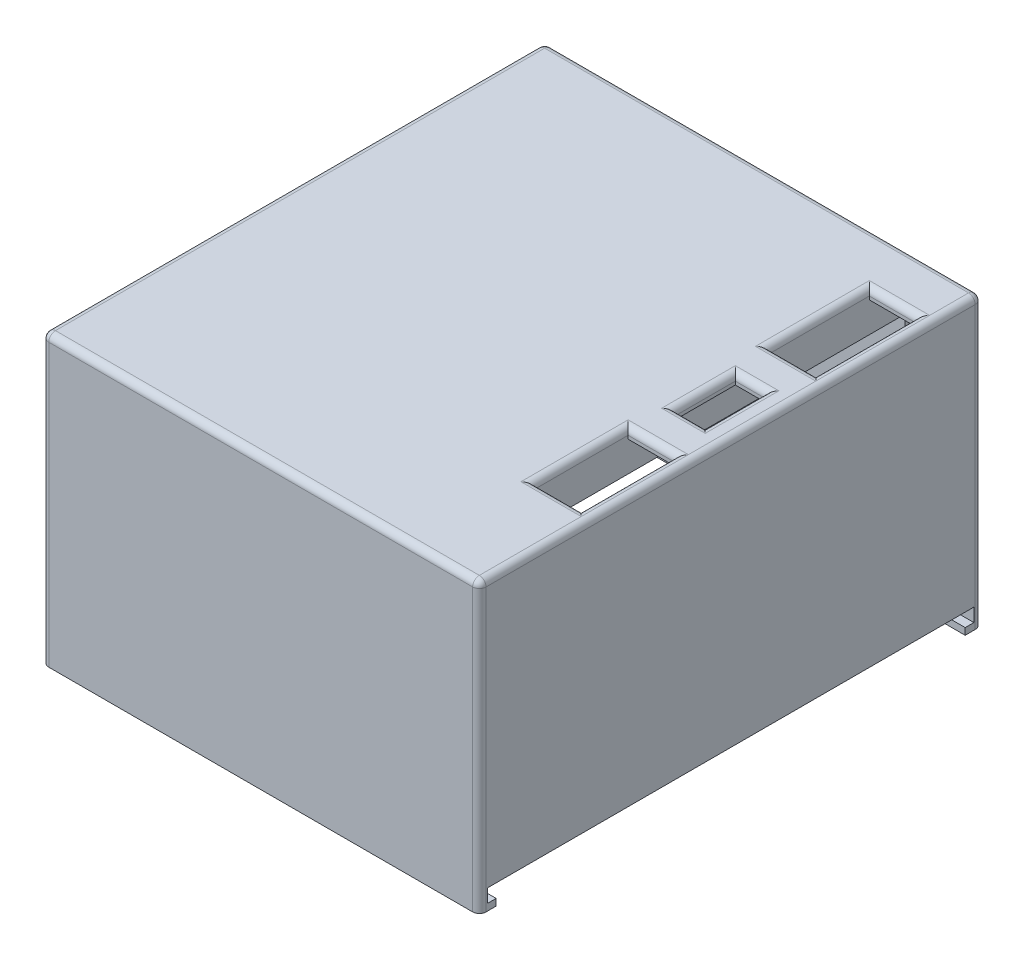
SolidWorks part; units mm, degrees
ref_plane "Front Plane" through (0, 0, 0) normal (0, 0, 1) x (1, 0, 0)
ref_plane "Top Plane" through (0, 0, 0) normal (0, 1, 0) x (1, 0, 0)
ref_plane "Right Plane" through (0, 0, 0) normal (1, 0, 0) x (0, 0, -1)
sketch "Sketch1" plane through (0, 0, 0) normal (0, 1, 0) x (1, 0, 0)
  line L1 (-32.63, -37.5) -> (32.63, -37.5)
  line L2 (-32.63, -37.5) -> (-32.63, 37.5)
  line L3 (-32.63, 37.5) -> (32.63, 37.5)
  line L4 (32.63, -37.5) -> (32.63, 37.5)
  point P5 (-32.63, 0)
  point P10 (0, -37.5)
  dimension "D1" = 75
  dimension "D2" = 65.26
extrude "Boss-Extrude1" add sketch "Sketch1" along normal blind 43
sketch "Sketch3" plane through (0, 0, 0) normal (0, 0, 1) x (1, 0, 0)
  line L0 (-32.63, 0) -> (32.63, 0) construction
  line L1 (30.63, 0) -> (-30.63, 0)
  line L4 (-30.63, 0) -> (-30.63, 31.95)
  line L5 (-32.63, 43) -> (-32.63, 0) construction
  line L6 (19.3, 41) -> (-32.63, 41) construction
  line L7 (7.61, 37) -> (4.28, 37)
  line L8 (-10.74, 37) -> (-14.07, 37)
  line L9 (-32.63, 43) -> (32.63, 43) construction
  line L10 (22.63, 37) -> (23.63, 37)
  line L11 (23.63, 37) -> (23.63, 41.5)
  line L12 (23.63, 41.5) -> (30.63, 41.5)
  line L13 (30.63, 41.5) -> (30.63, 0)
  arc A0 (-14.07, 37) -> (-30.63, 31.95) centre (-21.58, 31.95) ccw
  arc A1 (4.28, 37) -> (-10.74, 37) centre (-3.23, 31.95) ccw
  arc A2 (22.63, 37) -> (7.61, 37) centre (15.12, 31.95) ccw
  dimension "D3" = 18.1
  dimension "D4" = 0.25
  dimension "D5" = 0.25
  dimension "D6" = 6
  dimension "D1" = 2
  dimension "D2" = 2
  dimension "D7" = 1.5
  dimension "D8" = 1
  dimension "D9" = 7
extrude "Cut-Extrude1" cut sketch "Sketch3" against normal blind 35 and the other way blind 35
sketch "Sketch4" plane through (0, 0, 0) normal (0, -1, 0) x (-1, 0, 0)
  line L6 (-23.63, -35) -> (-23.63, 35) construction
  line L7 (-23.63, 36.7) -> (-30.63, 36.7)
  line L8 (-23.63, 36.7) -> (-23.63, 35)
  line L9 (-23.63, 35) -> (-30.63, 35)
  line L10 (-30.63, 36.7) -> (-30.63, 35)
  line L11 (-32.63, 37.5) -> (32.63, 37.5) construction
  dimension "D1" = 0.8
extrude "Cut-Extrude2" cut sketch "Sketch4" against normal up to surface (41.5 mm away) up to face at (27.13, 41.5, 0)
sketch "Sketch5" plane through (0, 41.5, 0) normal (0, -1, 0) x (-1, 0, 0)
  line L0 (-30.63, -35) -> (-30.63, 36.7) construction
  line L1 (-23.63, -6.3) -> (-30.63, -6.3)
  line L2 (-23.63, -6.3) -> (-23.63, -20.3)
  line L3 (-23.63, -20.3) -> (-30.63, -20.3)
  line L4 (-30.63, -6.3) -> (-30.63, -20.3)
  line L5 (-30.63, -35) -> (-30.63, 36.7) construction
  line L6 (-23.63, 29.7) -> (-30.63, 29.7)
  line L7 (-23.63, 29.7) -> (-23.63, 14.7)
  line L8 (-23.63, 14.7) -> (-30.63, 14.7)
  line L9 (-30.63, 29.7) -> (-30.63, 14.7)
  line L11 (-24.63, 8.7) -> (-29.13, 8.7)
  line L12 (-24.63, 8.7) -> (-24.63, -0.3)
  line L13 (-24.63, -0.3) -> (-29.13, -0.3)
  line L14 (-29.13, 8.7) -> (-29.13, -0.3)
  line L17 (-23.63, 36.7) -> (-30.63, 36.7) construction
  line L18 (-30.63, 36.7) -> (-23.63, 36.7) construction
  dimension "D1" = 7
  dimension "D2" = 22
  dimension "D3" = 28
  dimension "D4" = 37
  dimension "D5" = 43
  dimension "D6" = 57
  dimension "D7" = 7
  dimension "D8" = 6
  dimension "D9" = 1.5
extrude "Cut-Extrude3" cut sketch "Sketch5" against normal through all
sketch "Sketch7" plane through (0, 0, -36.7) normal (0, 0, 1) x (1, 0, 0)
  line L0 (30.63, 41.5) -> (23.63, 41.5) construction
  line L1 (23.63, 29.5) -> (30.63, 29.5)
  line L2 (23.63, 29.5) -> (23.63, 32)
  line L3 (23.63, 35.5) -> (30.63, 35.5)
  line L4 (30.63, 29.5) -> (30.63, 32)
  line L5 (30.63, 41.5) -> (23.63, 41.5) construction
  line L6 (30.63, 41.5) -> (30.63, 0) construction
  line L8 (24.63, 41.5) -> (29.13, 41.5) construction
  line L9 (24.63, 14.5) -> (30.63, 14.5)
  line L10 (24.63, 14.5) -> (24.63, 26.5)
  line L11 (24.63, 26.5) -> (30.63, 26.5)
  line L12 (30.63, 14.5) -> (30.63, 26.5)
  line L13 (23.63, 37) -> (23.63, 0) construction
  line L14 (23.63, 32.5) -> (31.13, 32.5) construction
  line L15 (23.63, 32) -> (24.9363, 32)
  line L17 (23.63, 33) -> (24.9363, 33)
  line L19 (29.3237, 32) -> (30.63, 32)
  line L21 (29.3237, 33) -> (30.63, 33)
  line L23 (23.63, 33) -> (23.63, 35.5)
  line L24 (30.63, 33) -> (30.63, 35.5)
  arc A0 (29.3237, 33) -> (24.9363, 33) centre (27.13, 32.5) ccw
  arc A1 (24.9363, 32) -> (29.3237, 32) centre (27.13, 32.5) ccw
  dimension "D4" = 4.5
  dimension "D1" = 6
  dimension "D2" = 12
  dimension "D3" = 3.5
  dimension "D5" = 15
  dimension "D6" = 6
  dimension "D7" = 1
  dimension "D8" = 27
extrude "Cut-Extrude4" cut sketch "Sketch7" against normal through all
fillet "Fillet1" radius 1 20 edges at (0, 43, -37.5) (32.63, 43, 0) (0, 43, 37.5) (-32.63, 43, 0) (29.13, 43, -4.2) (26.88, 43, -8.7) (24.63, 43, -4.2) (26.88, 43, 0.3) (30.63, 43, -22.2) (27.13, 43, -29.7) (23.63, 43, -22.2) (27.13, 43, -14.7) (30.63, 43, 13.3) (27.13, 43, 6.3) (23.63, 43, 13.3) (27.13, 43, 20.3) (32.63, 21.5, 37.5) (32.63, 21.5, -37.5) (-32.63, 21.5, 37.5) (-32.63, 21.5, -37.5)
sketch "Sketch8" plane through (0, 0, 0) normal (0, -1, 0) x (-1, 0, 0)
  line L1 (0, 0) -> (-45.2311, 0) construction
  line L2 (-30.63, -35) -> (-30.63, 36.7) construction
  line L3 (-30.63, 7) -> (-29.13, 7)
  line L4 (-30.63, 7) -> (-30.63, 13)
  line L5 (-30.63, 13) -> (-29.13, 13)
  line L8 (-30.63, -13) -> (-29.13, -13)
  line L9 (-30.63, -13) -> (-30.63, -7)
  line L10 (-30.63, -7) -> (-29.13, -7)
  arc A1 (-29.13, -13) -> (-29.13, -7) centre (-29.13, -10) ccw
  arc A2 (-29.13, 7) -> (-29.13, 13) centre (-29.13, 10) ccw
  dimension "D1" = 6
  dimension "D2" = 10
  dimension "D3" = 1.5
extrude "Boss-Extrude2" add sketch "Sketch8" against normal blind 10
sketch "Sketch11" plane through (0, 0, 0) normal (0, 0, 1) x (1, 0, 0)
  line L0 (30.63, 10) -> (26.13, 6)
  line L2 (26.13, 6) -> (26.13, 10)
  line L4 (26.13, 10) -> (30.63, 10)
  line L6 (26.13, 10) -> (26.13, 0) construction
  line L7 (30.63, 10) -> (29.13, 10) construction
  line L8 (30.63, 41.5) -> (30.63, 0) construction
  line L9 (30.63, 0) -> (-30.63, 0) construction
  dimension "D1" = 6
extrude "Cut-Extrude5" cut sketch "Sketch11" against normal blind 20 and the other way blind 20
sketch "Sketch12" plane through (32.63, 0, 0) normal (1, 0, 0) x (0, 0, -1)
  line L1 (36.3, 1) -> (-36.3, 1)
  line L2 (36.3, 1) -> (36.3, 3)
  line L3 (36.3, 3) -> (-36.3, 3)
  line L4 (-36.3, 1) -> (-36.3, 3)
  line L5 (-37.5, 0) -> (-37.5, 42) construction
  line L6 (37.5, 42) -> (37.5, 0) construction
  line L7 (-36.5, 0) -> (36.5, 0) construction
  dimension "D1" = 1.2
  dimension "D2" = 1.2
  dimension "D3" = 1
  dimension "D4" = 2
extrude "Cut-Extrude6" cut sketch "Sketch12" against normal blind 64
sketch "Sketch13" plane through (0, 0, 0) normal (0, -1, 0) x (1, 0, 0)
  line L0 (32.63, 36.5) -> (32.63, -36.5) construction
  line L1 (32.63, -35) -> (26.13, -35)
  line L2 (32.63, -35) -> (32.63, 35)
  line L3 (32.63, 35) -> (26.13, 35)
  line L4 (26.13, -35) -> (26.13, 35)
  line L5 (-30.63, 35) -> (30.63, 35) construction
  line L6 (-30.63, -35) -> (23.63, -35) construction
  arc A0 (29.13, -7) -> (29.13, -13) centre (29.13, -10) ccw construction
extrude "Cut-Extrude7" cut sketch "Sketch13" against normal up to surface (3 mm away) up to face at (15.7122, 3, -4.0333)
sketch "Sketch15" plane through (23.63, 0, 0) normal (1, 0, 0) x (0, 0, -1)
  line L0 (36.7, 29.5) -> (36.7, 0) construction
  line L2 (36.7, 0) -> (36.7, 3)
  line L3 (36.7, 3) -> (36.3, 3)
  line L4 (36.3, 1) -> (36.3, 3)
  line L5 (35, 0) -> (36.7, 0) construction
  line L6 (36.7, 0) -> (35, 0)
  line L8 (36.3, 1) -> (35, 1)
  line L9 (35, 0) -> (35, 1)
extrude "Boss-Extrude3" add sketch "Sketch15" along normal up to surface (7 mm away) up to face at (30.63, 22.75, -17.4111)
sketch "Sketch17" plane through (0, 3, 0) normal (0, -1, 0) x (-1, 0, 0)
  circle A0 centre (-29.13, 10) radius 2
  circle A1 centre (-29.13, -10) radius 2
  arc A2 (-29.13, -13) -> (-29.13, -7) centre (-29.13, -10) ccw construction
  arc A3 (-29.13, 7) -> (-29.13, 13) centre (-29.13, 10) ccw construction
  dimension "D1" = 4
extrude "Cut-Extrude9" cut sketch "Sketch17" against normal blind 2.5
